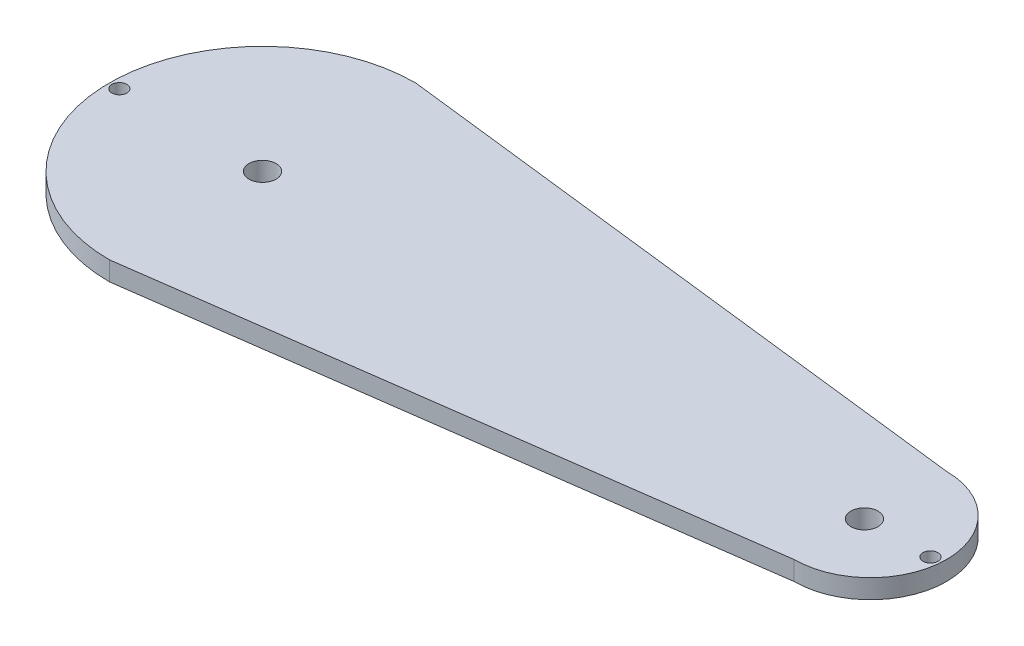
SolidWorks part; units mm, degrees
ref_plane "Front Plane" through (0, 0, 0) normal (0, 0, 1) x (1, 0, 0)
ref_plane "Top Plane" through (0, 0, 0) normal (0, 1, 0) x (1, 0, 0)
ref_plane "Right Plane" through (0, 0, 0) normal (1, 0, 0) x (0, 0, -1)
sketch "Sketch1" plane through (0, 0, 0) normal (0, 1, 0) x (1, 0, 0)
  line L0 (0, 50.8924) -> (200.0001, 27.3028)
  line L1 (200.0001, -23.3712) -> (0, -50.8924)
  arc A0 (0, -50.8924) -> (0, 50.8924) centre (0, 0) cw
  arc A1 (200.0001, -23.3712) -> (200.0001, 27.3028) centre (200.0001, 1.9658) ccw
extrude "Boss-Extrude1" add sketch "Sketch1" along normal blind 25.4 contours L1 A0 L0 A1
sketch "Sketch2" plane through (0, 25.4, 0) normal (0, 1, 0) x (1, 0, 0)
  line L0 (0, 44.5318) -> (200.0001, 20.9585)
  line L1 (200.0001, -17.0269) -> (0, -44.5318)
  arc A0 (0, -44.5318) -> (0, 44.5318) centre (0, 0) cw
  arc A1 (200.0001, -17.0269) -> (200.0001, 20.9585) centre (200.0001, 1.9658) ccw
  circle A2 centre (-47.498, 0) radius 2.54
  dimension "D1" = 5.08
sketch "Sketch3" plane through (0, 25.4, 0) normal (0, 1, 0) x (1, 0, 0)
  circle A0 centre (-47.5691, 0) radius 2.5
  arc A2 (0, 50.8924) -> (0, -50.8924) centre (0, 0) ccw construction
  circle A3 centre (221.9261, 0) radius 2.5
  arc A4 (200.0001, -23.3712) -> (200.0001, 27.3028) centre (200.0001, 1.9658) ccw construction
  point P11 (-50.8924, 0)
  point P15 (225.3371, 1.9658)
  dimension "D1" = 5
  dimension "D4" = 5
  dimension "D3" = 3.3233
  dimension "D5" = 3.4109
extrude "Cut-Extrude2" cut sketch "Sketch3" against normal blind 25.4
sketch "Sketch4" plane through (0, 25.4, 0) normal (0, 1, 0) x (1, 0, 0)
  circle A0 centre (0, 0) radius 4.5
  circle A1 centre (200.0001, 0) radius 4.5
extrude "Cut-Extrude3" cut sketch "Sketch1<3>" along normal blind 19.05
sketch "Sketch1<3>" plane through (0, 0, 0) normal (0, 1, 0) x (1, 0, 0) same geometry as "Sketch1"
extrude "Cut-Extrude4" cut sketch "Sketch4" against normal blind 19.05 contours A1 | A0
